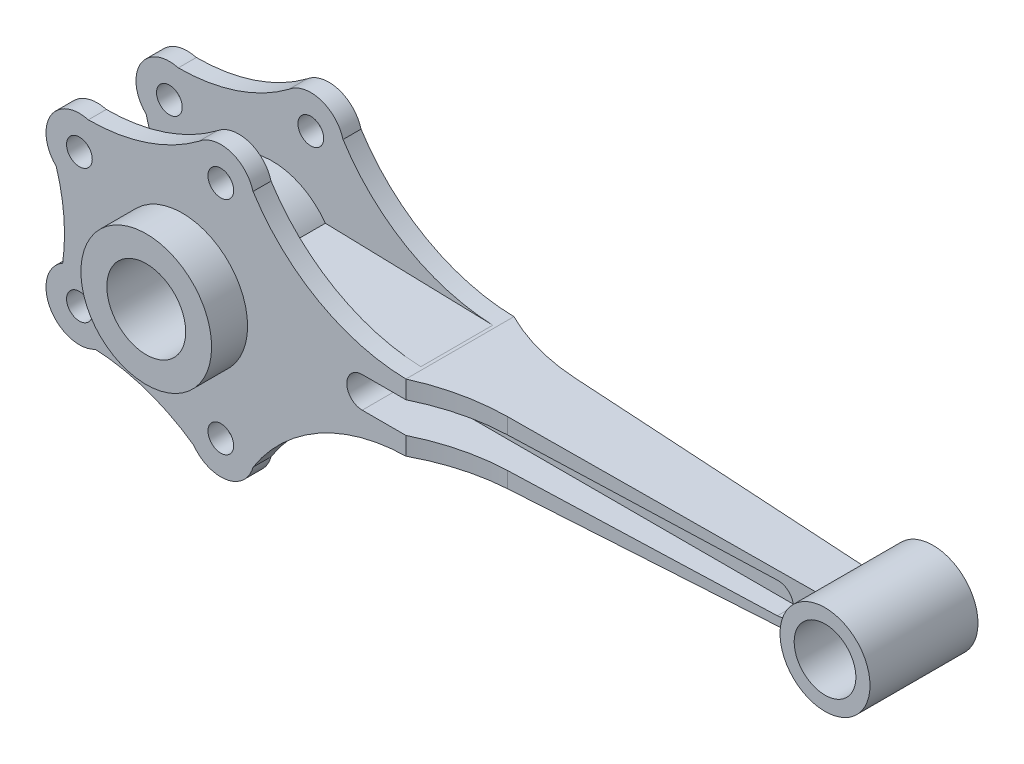
SolidWorks part; units mm, degrees
ref_plane "Front Plane" through (0, 0, 0) normal (0, 0, 1) x (1, 0, 0)
ref_plane "Top Plane" through (0, 0, 0) normal (0, 1, 0) x (1, 0, 0)
ref_plane "Right Plane" through (0, 0, 0) normal (1, 0, 0) x (0, 0, -1)
sketch "Sketch1" plane through (0, 0, 0) normal (0, 0, 1) x (1, 0, 0)
  line L0 (0, 0) -> (250, 0) construction
  line L2 (234.9917, 9) -> (20.6676, 14.7929)
  line L3 (234.9917, -9) -> (20.6676, -14.7929)
  circle A0 centre (0, 0) radius 15.3459
  circle A1 centre (0, 0) radius 25.4161
  circle A2 centre (250, 0) radius 17.5
  circle A3 centre (250, 0) radius 12
  circle A4 centre (15, 43) radius 5
  arc A5 (27.5388, 46.4319) -> (6.4846, 52.8229) centre (15, 43) ccw
  circle A6 centre (-40, 26) radius 5
  arc A7 (-36.521, 38.5258) -> (-49.0111, 16.6298) centre (-40, 26) ccw
  circle A8 centre (-40, -26) radius 5
  arc A9 (-46.5082, -14.7464) -> (-33.7747, -37.4125) centre (-40, -26) ccw
  circle A10 centre (15, -43) radius 5
  arc A11 (4.4144, -50.5461) -> (27.5388, -46.4319) centre (15, -43) ccw
  arc A12 (-36.521, 38.5258) -> (6.4846, 52.8229) centre (-36.5778, 110.5258) ccw
  arc A13 (-49.0111, 16.6298) -> (-46.5082, -14.7464) centre (-117.7961, -4.6451) cw
  arc A14 (-33.7747, -37.4125) -> (4.4144, -50.5461) centre (-37.156, -109.3331) cw
  arc A15 (87, 13) -> (27.5388, 46.4319) centre (88.3457, 84.9874) cw
  arc A16 (87, -13) -> (27.5388, -46.4319) centre (88.3457, -84.9874) ccw
  dimension "D3" = 24
  dimension "D4" = 35
  dimension "D5" = 250
  dimension "D21" = 26
  dimension "D24" = 9
extrude "Boss-Extrude3" add sketch "Sketch1" along normal mid plane 70 contours A0 A1 region at (23.5154, 7.5484, 0)
extrude "Boss-Extrude4" add sketch "Sketch1<6>" along normal mid plane 42 contours L0 A1 L3 A16 A2 | A1 L0 A2 L2 A15 region at (120.2869, 6.0905, 0) region at (120.2869, -6.0905, 0)
sketch "Sketch1<6>" plane through (0, 0, 0) normal (0, 0, 1) x (1, 0, 0) same geometry as "Sketch1"
sketch "Sketch2" plane through (0, 0, 0) normal (0, 1, 0) x (1, 0, 0)
  line L0 (234.9917, 9) -> (118.6566, 13.0625)
  line L1 (234.9917, -21) -> (234.9917, 21) construction
  line L2 (0, 0) -> (234.9917, 0) construction
  line L4 (85.8008, 21) -> (234.9917, 21)
  line L5 (234.9917, 21) -> (234.9917, 9)
  line L6 (234.9917, -21) -> (234.9917, -9)
  line L7 (85.8008, -21) -> (234.9917, -21)
  line L8 (234.9917, -9) -> (118.6566, -13.0625)
  arc A0 (118.6566, 13.0625) -> (87, 21) centre (121.3788, 91.015) cw
  arc A1 (118.6566, -13.0625) -> (87, -21) centre (121.3788, -91.015) ccw
  dimension "D2" = 78
  dimension "D1" = 2
  dimension "D3" = 9
extrude "Cut-Extrude1" cut sketch "Sketch2" against normal mid plane 42 contours A0 L0 L5 L4 | L8 A1 L7 L6 region at (171.6515, 0, -16.1871) region at (171.6515, 0, 16.1871)
extrude "Boss-Extrude5" add sketch "Sketch1<7>" along normal mid plane 42 contours A2 A3 region at (254.5372, 16.3886, 0)
sketch "Sketch1<7>" plane through (0, 0, 0) normal (0, 0, 1) x (1, 0, 0) same geometry as "Sketch1"
extrude "Boss-Extrude6" add sketch "Sketch1<8>" along normal blind 7 from offset 14 contours A16 L3 A1 L2 A15 A5 A12 A7 A13 A9 A14 A11 A10 A8 A6 A4 region at (53.2824, 15.6955, 0)
sketch "Sketch1<8>" plane through (0, 0, 0) normal (0, 0, 1) x (1, 0, 0) same geometry as "Sketch1"
mirror "Mirror1" about plane through (0, 0, 0) normal (0, 0, 1) of "Boss-Extrude6"
sketch "Sketch3" plane through (0, 0, 21) normal (0, 0, 1) x (1, 0, 0)
  line L0 (70, 0) -> (220, 0) construction
  line L1 (70, 6) -> (220, 6)
  line L2 (70, -6) -> (220, -6)
  arc A0 (70, 6) -> (70, -6) centre (70, 0) ccw
  arc A1 (220, -6) -> (220, 6) centre (220, 0) ccw
  circle A2 centre (250, 0) radius 12 construction
  point P2 (145, 0)
  dimension "D2" = 30
  dimension "D3" = 6
  dimension "D1" = 150
extrude "Cut-Extrude2" cut sketch "Sketch3" against normal offset from surface (18.5 mm away) 2.5 up to plane "Front Plane"
mirror "Mirror2" about plane through (0, 0, 0) normal (0, 0, 1) of "Cut-Extrude2"
